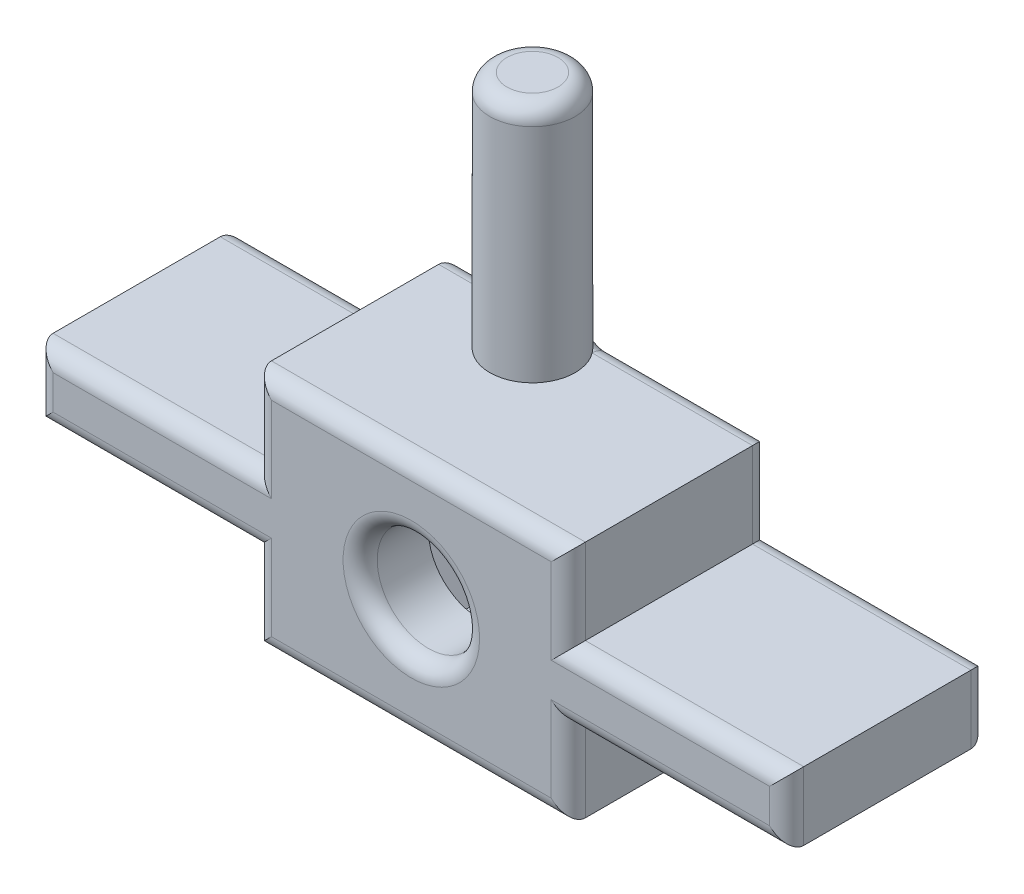
SolidWorks part; units mm, degrees
ref_plane "Front Plane" through (0, 0, 0) normal (0, 0, 1) x (1, 0, 0)
ref_plane "Top Plane" through (0, 0, 0) normal (0, 1, 0) x (1, 0, 0)
ref_plane "Right Plane" through (0, 0, 0) normal (1, 0, 0) x (0, 0, -1)
sketch "Sketch1" plane through (0, 0, 0) normal (0, 0, 1) x (1, 0, 0)
  line L0 (-4.6, 3.5) -> (4.6, 3.5)
  line L1 (-4.6, 3.5) -> (-4.6, -3.5)
  line L2 (4.6, 3.5) -> (4.6, -3.5)
  line L3 (-4.6, -3.5) -> (4.6, -3.5)
  line L4 (-4.6, 3.5) -> (4.6, -3.5) construction
  line L5 (4.6, 3.5) -> (-4.6, -3.5) construction
  line L6 (11, 1) -> (4.6, 1)
  line L7 (1.4434, -2.5) -> (2.8868, 0)
  line L8 (2.8868, 0) -> (1.4434, 2.5)
  line L9 (1.4434, 2.5) -> (-1.4434, 2.5)
  line L10 (-1.4434, 2.5) -> (-2.8868, 0)
  line L11 (-2.8868, 0) -> (-1.4434, -2.5)
  line L12 (-1.4434, -2.5) -> (1.4434, -2.5)
  line L13 (11, 1) -> (11, -1)
  line L14 (4.6, 1) -> (4.6, -1)
  line L15 (11, -1) -> (4.6, -1)
  line L16 (11, 1) -> (4.6, -1) construction
  line L17 (4.6, 1) -> (11, -1) construction
  line L18 (-11, 1) -> (-4.6, 1)
  line L19 (-11, 1) -> (-11, -1)
  line L20 (-4.6, 1) -> (-4.6, -1)
  line L21 (-11, -1) -> (-4.6, -1)
  line L22 (-11, 1) -> (-4.6, -1) construction
  line L23 (-4.6, 1) -> (-11, -1) construction
  circle A0 centre (0, 0) radius 2.5 construction
  point P1 (0, 0)
  point P15 (7.8, 0)
  point P16 (-7.8, 0)
  dimension "D2" = 5
  dimension "D1" = 6.4
  dimension "D3" = 7
  dimension "D4" = 22
  dimension "D5" = 2
extrude "Boss-Extrude1" add sketch "Sketch1" along normal mid plane 1.9 contours L1 L3 L2 L0 L12 L11 L10 L9 L8 L7 | L19 L21 L1 L18 | L15 L13 L6 L2 region at (0, 3.3844, 0) region at (-7.8, 0, 0) region at (7.8, 0, 0)
sketch "Sketch2" plane through (0, 0, 0.95) normal (0, 0, 1) x (1, 0, 0)
  line L12 (-4.6, 3.5) -> (-4.6, 1)
  line L13 (-4.6, 1) -> (-11, 1)
  line L14 (-11, 1) -> (-11, -1)
  line L15 (-11, -1) -> (-4.6, -1)
  line L16 (-4.6, -1) -> (-4.6, -3.5)
  line L17 (-4.6, -3.5) -> (4.6, -3.5)
  line L18 (4.6, -3.5) -> (4.6, -1)
  line L19 (4.6, -1) -> (11, -1)
  line L20 (11, -1) -> (11, 1)
  line L21 (11, 1) -> (4.6, 1)
  line L22 (4.6, 1) -> (4.6, 3.5)
  line L23 (4.6, 3.5) -> (-4.6, 3.5)
  line L24 (-4.6, 3.5) -> (-4.6, 1)
  line L25 (-4.6, 1) -> (-11, 1)
  line L26 (-11, 1) -> (-11, -1)
  line L27 (-11, -1) -> (-4.6, -1)
  line L28 (-4.6, -1) -> (-4.6, -3.5)
  line L29 (-4.6, -3.5) -> (4.6, -3.5)
  line L30 (4.6, -3.5) -> (4.6, -1)
  line L31 (4.6, -1) -> (11, -1)
  line L32 (11, -1) -> (11, 1)
  line L33 (11, 1) -> (4.6, 1)
  line L34 (4.6, 1) -> (4.6, 3.5)
  line L35 (4.6, 3.5) -> (-4.6, 3.5)
  circle A0 centre (0, 0) radius 1.5
  dimension "D2" = 3
  dimension "D1" = 0
extrude "Boss-Extrude2" add sketch "Sketch2" along normal blind 2
mirror "Mirror1" about plane through (0, 0, 0) normal (0, 0, 1) of "Boss-Extrude2"
sketch "Sketch3" plane through (0, 3.5, 0) normal (0, 1, 0) x (1, 0, 0)
  line L0 (4.6, 2.95) -> (-4.6, 2.95) construction
  line L1 (-4.6, -2.95) -> (-4.6, 2.95) construction
  circle A0 centre (-1.1, 1.7) radius 1.25
  dimension "D1" = 2.5
  dimension "D2" = 3.5
extrude "Boss-Extrude3" add sketch "Sketch3" along normal blind 7
fillet "Fillet1" radius 0.5 28 edges at (-2.85, 3.5, -2.95) (-4.6, 2.25, -2.95) (-7.8, 1, -2.95) (-11, 0, -2.95) (-7.8, -1, -2.95) (-4.6, -2.25, -2.95) (0, -3.5, -2.95) (4.6, -2.25, -2.95) (7.8, -1, -2.95) (11, 0, -2.95) (7.8, 1, -2.95) (4.6, 2.25, -2.95) (1.75, 3.5, -2.95) (1.5, 0, -2.95) (1.5, 0, 2.95) (4.6, 2.25, 2.95) (7.8, 1, 2.95) (11, 0, 2.95) (7.8, -1, 2.95) (4.6, -2.25, 2.95) (0, -3.5, 2.95) (-4.6, -2.25, 2.95) (-7.8, -1, 2.95) (-11, 0, 2.95) (-7.8, 1, 2.95) (-4.6, 2.25, 2.95) (0, 3.5, 2.95) (-1.1, 10.5, -0.45)
